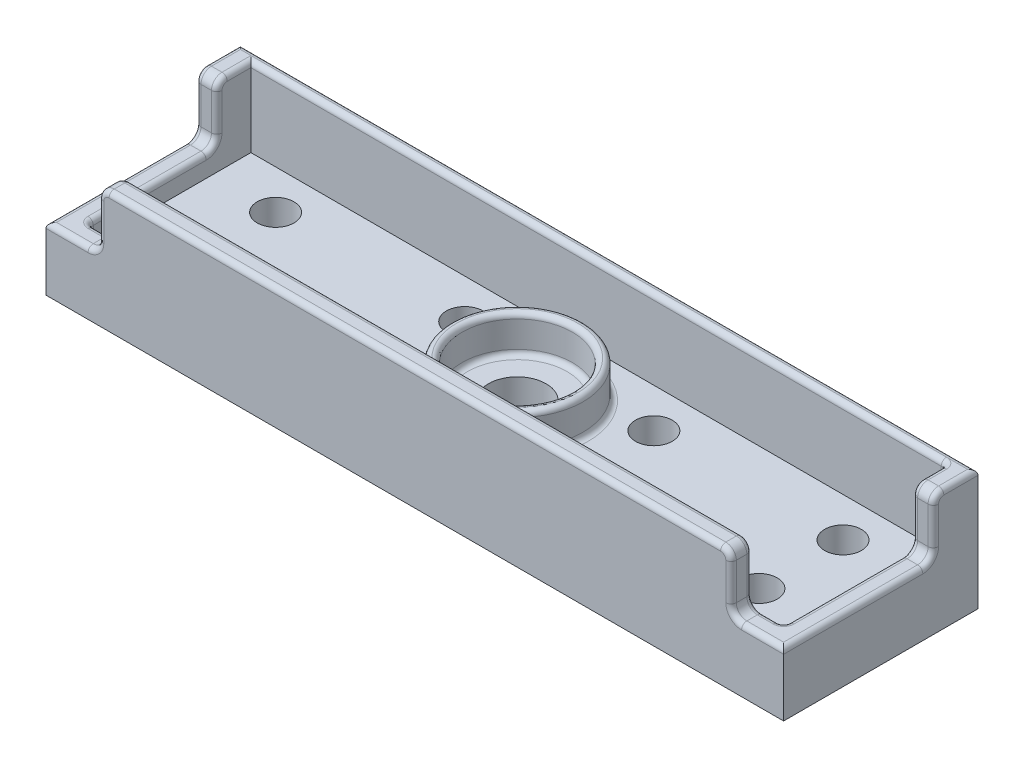
SolidWorks part; units mm, degrees
material "Nylon 6/10"
ref_plane "Front Plane" through (0, 0, 0) normal (0, 0, 1) x (1, 0, 0)
ref_plane "Top Plane" through (0, 0, 0) normal (0, 1, 0) x (1, 0, 0)
ref_plane "Right Plane" through (0, 0, 0) normal (1, 0, 0) x (0, 0, -1)
sketch "Sketch1" plane through (0, 0, 0) normal (0, 1, 0) x (1, 0, 0)
  line L1 (-35.1, -9.25) -> (0, -9.25)
  line L2 (-35.1, -9.25) -> (-35.1, 9.25)
  line L3 (-35.1, 9.25) -> (0, 9.25)
  line L4 (0, -9.25) -> (0, 9.25)
  line L5 (-35.1, -9.25) -> (0, 9.25) construction
  line L6 (-35.1, 9.25) -> (0, -9.25) construction
  point P0 (-17.55, 0)
  point P8 (0, 0)
  dimension "D1" = 35.1
  dimension "D2" = 18.5
extrude "Boss-Extrude1" add sketch "Sketch1" along normal blind 11.5
shell "Shell1" [suppressed] thickness 1
sketch "Sketch7" plane through (0, 11.5, 0) normal (0, 1, 0) x (1, 0, 0)
  line L0 (0, -9.25) -> (0, 9.25) construction
  line L1 (0, -7.25) -> (-33.1, -7.25)
  line L2 (0, -7.25) -> (0, 8.25)
  line L3 (0, 8.25) -> (-33.1, 8.25)
  line L4 (-33.1, -7.25) -> (-33.1, 8.25)
  line L5 (-35.1, -9.25) -> (0, -9.25) construction
  line L6 (0, 9.25) -> (-35.1, 9.25) construction
  line L7 (-35.1, 9.25) -> (-35.1, -9.25) construction
  dimension "D1" = 2
  dimension "D2" = 1
  dimension "D3" = 2
extrude "Cut-Extrude5" cut sketch "Sketch7" against normal offset from surface (7.5 mm away) 4 up to face at (-17.55, 0, 0)
sketch "Sketch2" plane through (0, 0, 0) normal (0, 1, 0) x (-1, 0, 0)
  line L0 (27, 3.5) -> (9, 3.5) construction
  line L2 (27, 3.5) -> (27, -4.5) construction
  line L3 (27, -4.5) -> (9, -4.5) construction
  line L4 (9, -4.5) -> (9, 3.5) construction
  line L5 (27, -0.5) -> (18.8977, -0.5) construction
  line L6 (17.55, -9.25) -> (17.55, 9.25) construction
  line L7 (0, 7.25) -> (0, -8.25) construction
  line L8 (27, -0.5) -> (0, -0.5) construction
  line L9 (0, -9.25) -> (35.1, -9.25) construction
  line L10 (35.1, 9.25) -> (0, 9.25) construction
  circle A0 centre (27, 3.5) radius 1.75
  circle A1 centre (9, 3.5) radius 1.75
  circle A2 centre (27, -4.5) radius 1.75
  circle A3 centre (9, -4.5) radius 1.75
  circle A5 centre (27, 3.5) radius 2.5 construction
  circle A6 centre (27, -4.5) radius 2.5 construction
  circle A7 centre (9, -4.5) radius 2.5 construction
  circle A8 centre (9, 3.5) radius 2.5 construction
  point P3 (0, 0)
  point P7 (18.8977, -0.5)
  point P9 (0, -1.2141)
  point P28 (0, -1.5036)
  point P29 (0, -0.5)
  point P30 (18.0562, -0.5)
  dimension "D1" = 3.5
  dimension "D4" = 9
  dimension "D5" = 5
  dimension "D2" = 18
  dimension "D3" = 8
extrude "Cut-Extrude1" cut sketch "Sketch2" along normal through all
sketch "Sketch3" [suppressed] plane through (0, 5, 0) normal (0, 1, 0) x (1, 0, 0)
  line L1 (-2.9573, -5.1559) -> (2.9865, -5.139)
  line L2 (2.9865, -5.139) -> (5.9438, 0.0169)
  line L3 (5.9438, 0.0169) -> (2.9573, 5.1559)
  line L4 (2.9573, 5.1559) -> (-2.9865, 5.139)
  line L5 (-2.9865, 5.139) -> (-5.9438, -0.0169)
  line L6 (-5.9438, -0.0169) -> (-2.9573, -5.1559)
  circle A0 centre (0, 0) radius 2.6 construction
  circle A1 centre (0, 0) radius 5.1475 construction
  dimension "D1" = 5.2
extrude "Cut-Extrude2" [suppressed] cut sketch "Sketch3" against normal blind 0.5
sketch "Sketch4" plane through (-35.1, 0, 0) normal (-1, 0, 0) x (0, 0, 1)
  line L0 (-9.25, 11.5) -> (9.25, 11.5) construction
  line L1 (-5, 11.5) -> (9.25, 11.5)
  line L3 (-5, 6) -> (9.25, 6)
  line L4 (9.25, 11.5) -> (9.25, 6)
  line L5 (0, 6) -> (0, 0) construction
  line L11 (-9.25, 0) -> (9.25, 0) construction
  line L12 (-5, 6) -> (-5, 11.5)
  point P8 (0, 0)
  point P11 (0, 0)
  point P14 (0, 0)
  point P16 (-4.645, 11.5)
  point P17 (9.25, 11.5)
  dimension "D1" = 5
  dimension "D2" = 5.5
extrude "Cut-Extrude3" cut sketch "Sketch4" against normal offset from surface (5 mm away) 3 up to face at (-33.1, 7.75, -0.5) offset beyond the face yes
mirror "Mirror1" about plane through (0, 0, 0) normal (1, 0, 0) of bodies 105
sketch "Sketch5" plane through (0, 0, 0) normal (0, 1, 0) x (1, 0, 0)
  line L0 (33.1, 0.5) -> (0, 0.5) construction
  line L1 (33.1, 8.25) -> (33.1, -7.25) construction
  line L4 (0, 0.5) -> (0, 0) construction
  circle A0 centre (0, 0.5) radius 2.75
  dimension "D1" = 5.5
extrude "Cut-Extrude4" cut sketch "Sketch5" along normal through all
sketch "Sketch6" plane through (0, 4, 0) normal (0, 1, 0) x (1, 0, 0)
  circle A0 centre (0, 0.5) radius 6.25
  circle A1 centre (0, 0.5) radius 5.25
  circle A2 centre (0, 0.5) radius 2.75 construction
  point P4 (0, 0)
  point P5 (0, 0.7531)
  dimension "D1" = 10.5
  dimension "D2" = 1
extrude "Boss-Extrude2" add sketch "Sketch6" along normal blind 3.5
fillet "Fillet3" radius 1 8 edges at (30.1, 6, 8.25) (-30.1, 6, 8.25) (30.1, 11.5, 8.25) (-30.1, 11.5, 8.25) (34.1, 11.5, -5) (34.1, 6, -5) (-34.1, 11.5, -5) (-34.1, 6, -5)
fillet "Fillet4" radius 0.5 4 edges at (0, 7.5, 4.75) (0, 7.5, 5.75) (0, 4, -6.75) (0, 4, 4.75)
fillet "Fillet5" radius 0.5 43 edges at (33.1, 6, 1.625) (35.1, 6, 2.625) (0, 11.5, -9.25) (0, 11.5, 9.25) (-35.1, 11.5, -7.625) (-33.1, 11.5, -7.125) (0, 11.5, 7.25) (33.1, 11.5, -7.125) (35.1, 11.5, -7.625) (-33.1, 6, 1.625) (-35.1, 6, 2.625) (-33.1, 5, 7.25) (33.1, 5, 7.25) (33.1, 7.75, -8.25) (32.1, 6, 7.25) (35.1, 6.2929, -4.7071) (35.1, 8.75, -5) (35.1, 11.2071, -5.2929) (33.1, 6.2929, -4.7071) (33.1, 8.75, -5) (33.1, 11.2071, -5.2929) (-35.1, 11.2071, -5.2929) (-35.1, 8.75, -5) (-35.1, 6.2929, -4.7071) (-33.1, 11.2071, -5.2929) (-33.1, 8.75, -5) (-33.1, 6.2929, -4.7071) (33.1, 6, 9.25) (30.3929, 6.2929, 9.25) (30.1, 8.75, 9.25) (29.8071, 11.2071, 9.25) (-29.8071, 11.2071, 9.25) (-30.1, 8.75, 9.25) (-30.3929, 6.2929, 9.25) (0, 11.5, -8.25) (-32.1, 6, 7.25) (-33.1, 6, 9.25) (30.3929, 6.2929, 7.25) (30.1, 8.75, 7.25) (29.8071, 11.2071, 7.25) (-29.8071, 11.2071, 7.25) (-30.1, 8.75, 7.25) (-30.3929, 6.2929, 7.25)
